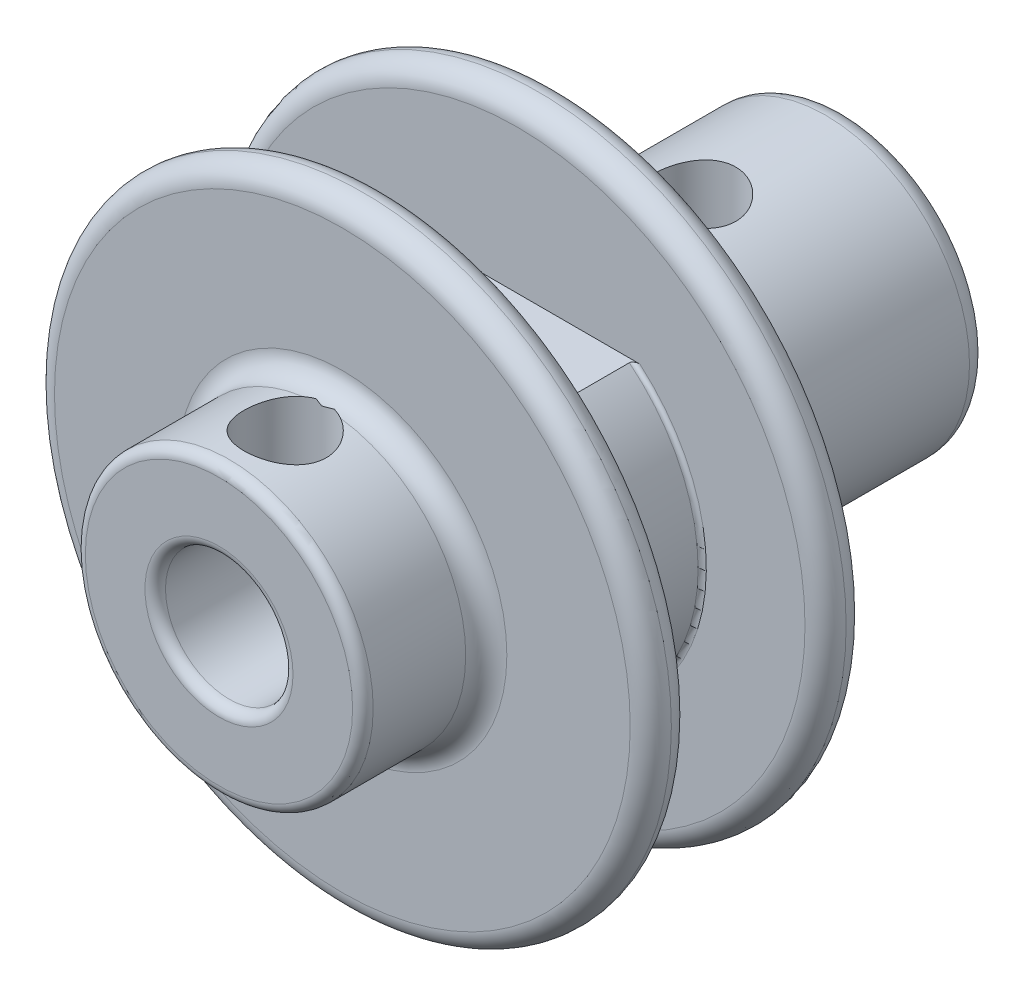
SolidWorks part; units mm, degrees
ref_plane "Front Plane" through (0, 0, 0) normal (0, 0, 1) x (1, 0, 0)
ref_plane "Top Plane" through (0, 0, 0) normal (0, 1, 0) x (1, 0, 0)
ref_plane "Right Plane" through (0, 0, 0) normal (1, 0, 0) x (0, 0, -1)
sketch "Sketch1" plane through (0, 0, 0) normal (0, 0, 1) x (1, 0, 0)
  circle A1 centre (0, -7) radius 3.1
  circle A2 centre (0, -7) radius 7
  dimension "D1" = 6.2
  dimension "D2" = 14
extrude "Boss-Extrude1" add sketch "Sketch1" along normal blind 6
sketch "Sketch2" plane through (0, 0, 0) normal (0, 0, -1) x (-1, 0, 0)
  circle A0 centre (0, -7) radius 15
  circle A1 centre (0, -7) radius 3.1
  dimension "D1" = 30
extrude "Boss-Extrude2" add sketch "Sketch2" along normal blind 2
sketch "Sketch3" plane through (0, 0, -2) normal (0, 0, -1) x (-1, 0, 0)
  line L0 (-5.6569, 0) -> (5.6569, 0)
  arc A0 (-5.6569, 0) -> (5.6569, 0) centre (0, -7) ccw
  circle A1 centre (0, -7) radius 3.1
  dimension "D1" = 18
  dimension "D2" = 7
  dimension "D3" = 6.2
extrude "Boss-Extrude3" add sketch "Sketch3" along normal blind 6.5
ref_plane "Plane1" through (0, 0, -5.25) normal (0, 0, -1) x (-1, 0, 0)
mirror "Mirror1" about plane through (0, 0, -5.25) normal (0, 0, -1) of "Boss-Extrude2"
sketch "Sketch5" plane through (0, 0, 0) normal (0, 1, 0) x (1, 0, 0)
  line L0 (15.4, 5.25) -> (-15.4, 5.25) construction
  circle A0 centre (0, 5.25) radius 2
  dimension "D1" = 4
extrude "Cut-Extrude2" cut sketch "Sketch5" against normal blind 7
sketch "Sketch6" plane through (0, 0, -10.5) normal (0, 0, -1) x (-1, 0, 0)
  circle A1 centre (0, -7) radius 7
  circle A2 centre (0, -7) radius 7
  circle A3 centre (0, -7) radius 3.1
  circle A4 centre (0, -7) radius 3.1
  dimension "D1" = 0
  dimension "D2" = 0
extrude "Boss-Extrude4" add sketch "Sketch6" along normal blind 14
fillet "Fillet1" radius 1 1 edges at (7, -7, 0)
fillet "Fillet2" radius 1 6 edges at (-15, -7, -10.5) (-15, -7, -8.5) (-15, -7, -2) (-15, -7, 0) (-7, -7, -24.5) (7, -7, -10.5)
fillet "Fillet3" radius 0.2 2 edges at (0, -16, -8.5) (0, -16, -2)
fillet "Fillet4" radius 0.5 3 edges at (3.1, -7, 6) (7, -7, 6) (-3.1, -7, -24.5)
sketch "Sketch4" plane through (0, 0, 0) normal (0, 1, 0) x (1, 0, 0)
  circle A0 centre (0, -2.7809) radius 2
  circle A1 centre (0, 17.1317) radius 2
  dimension "D1" = 4
  dimension "D2" = 4
extrude "Cut-Extrude1" cut sketch "Sketch4" against normal blind 8
